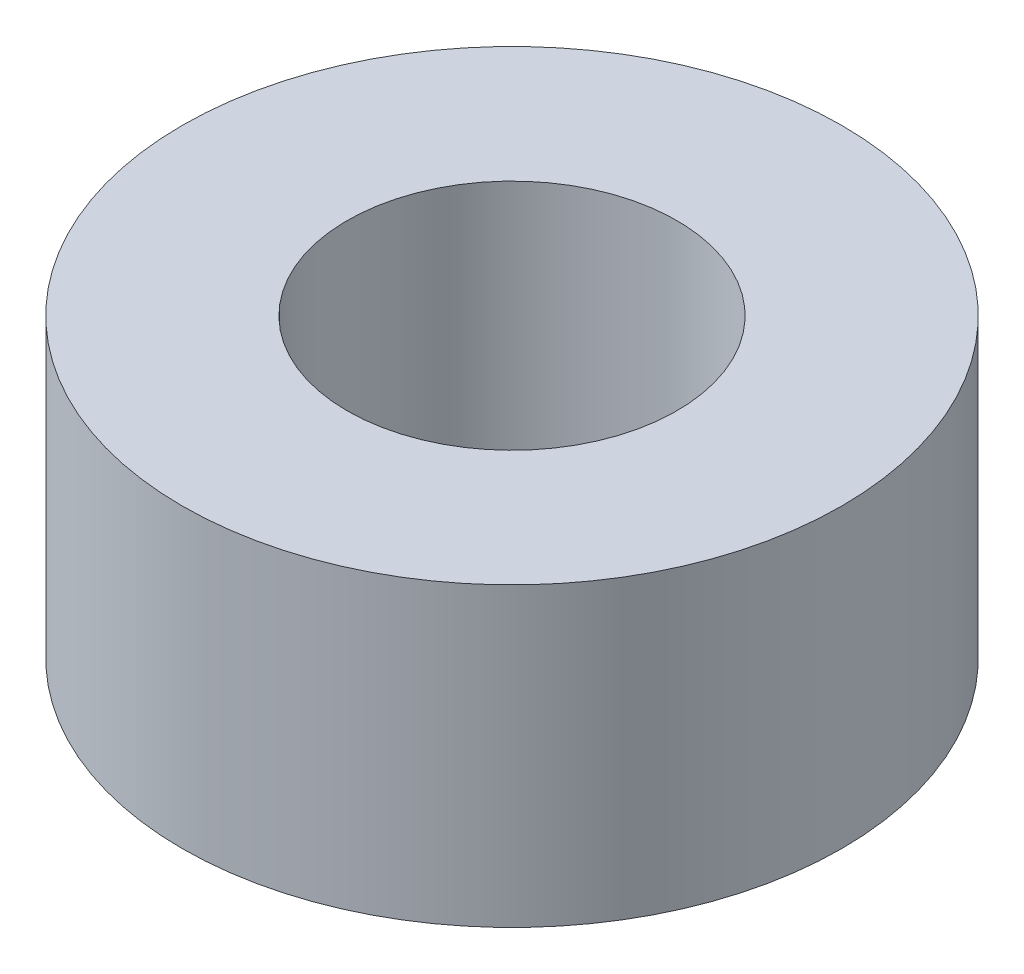
SolidWorks part; units mm, degrees
ref_plane "Front Plane" through (0, 0, 0) normal (0, 0, 1) x (1, 0, 0)
ref_plane "Top Plane" through (0, 0, 0) normal (0, 1, 0) x (1, 0, 0)
ref_plane "Right Plane" through (0, 0, 0) normal (1, 0, 0) x (0, 0, -1)
sketch "Sketch1" plane through (0, 0, 0) normal (0, 1, 0) x (1, 0, 0)
  circle A0 centre (0, 0) radius 10
  circle A1 centre (0, 0) radius 5
  dimension "D1" = 20
  dimension "D2" = 10
extrude "Boss-Extrude1" add sketch "Sketch1" along normal blind 9
